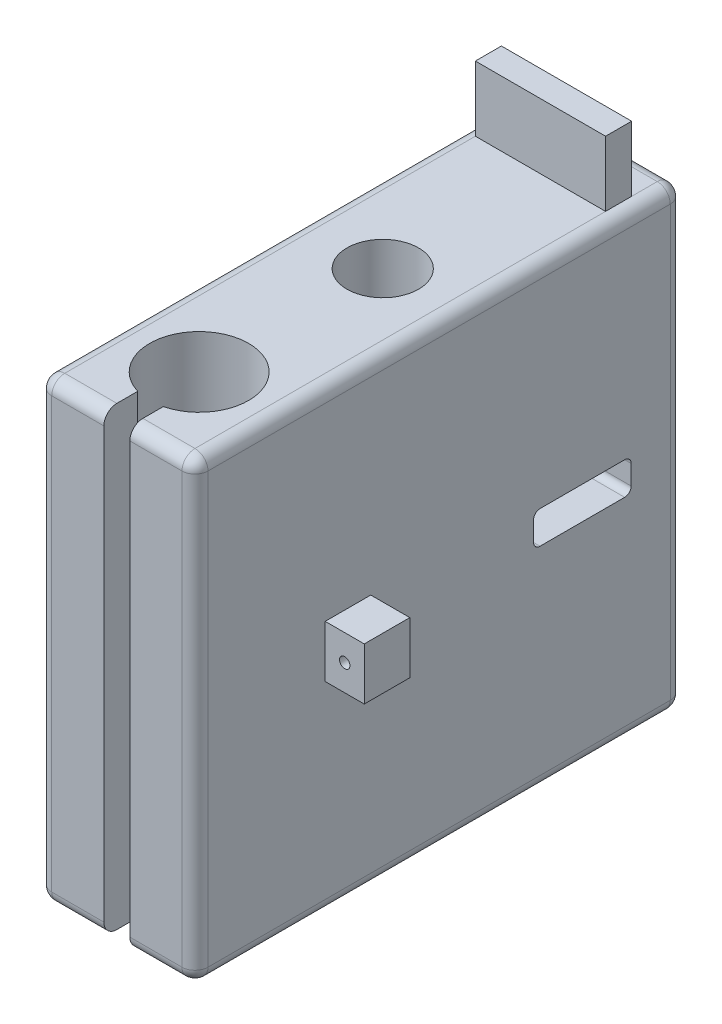
SolidWorks part; units mm, degrees
ref_plane "Front Plane" through (0, 0, 0) normal (0, 0, 1) x (1, 0, 0)
ref_plane "Top Plane" through (0, 0, 0) normal (0, 1, 0) x (1, 0, 0)
ref_plane "Right Plane" through (0, 0, 0) normal (1, 0, 0) x (0, 0, -1)
ref_plane "Plano1" through (-220, 0, 0) normal (1, 0, 0) x (0, 0, -1)
sketch "Esboço1" plane through (-220, 0, 0) normal (1, 0, 0) x (0, 0, -1)
  line L0 (-460.4999, 246.154) -> (-460.4999, 230.354) construction
  line L1 (-465.4999, 248.254) -> (-390.4999, 248.254)
  line L2 (-465.4999, 248.254) -> (-465.4999, 178.254)
  line L3 (-465.4999, 178.254) -> (-390.4999, 178.254)
  line L4 (-390.4999, 248.254) -> (-390.4999, 178.254)
  dimension "D1" = 75
  dimension "D2" = 70
  dimension "D3" = 5
extrude "Ressalto-extrusão1" add sketch "Esboço1" along normal blind 12 and the other way blind 12
sketch "Esboço3" plane through (0, 248.254, 0) normal (0, 1, 0) x (1, 0, 0)
  line L5 (-232, -465.4999) -> (-208, -465.4999) construction
  line L7 (-220, -465.4999) -> (-218, -465.4999)
  line L10 (-218, -465.4999) -> (-218, -460.3692)
  line L11 (-220, -465.4999) -> (-222, -465.4999)
  line L14 (-222, -465.4999) -> (-222, -460.292)
  arc A3 (-218, -460.3692) -> (-222, -460.292) centre (-219.8586, -452.9999) ccw
  circle A8 centre (-219.5085, -425.1499) radius 5.5
  circle A9 centre (-219.5085, -425.1499) radius 5.5
  dimension "D1" = 15.2
  dimension "D3" = 2
  dimension "D4" = 2
  dimension "D2" = 0.5
extrude "Corte-extrusão1" cut sketch "Esboço3" against normal through all
sketch "Esboço4" plane through (0, 0, 390.4999) normal (0, 0, -1) x (-1, 0, 0)
  line L0 (220, 248.254) -> (220, 178.254) construction
  line L1 (232, 248.254) -> (208, 248.254) construction
  line L2 (232, 178.254) -> (208, 178.254) construction
  circle A0 centre (219.8586, 238.254) radius 4.1
  circle A1 centre (219.8586, 188.254) radius 4.1
  dimension "D1" = 8.2
  dimension "D2" = 8.2
extrude "Corte-extrusão2" cut sketch "Esboço4" against normal blind 20
fillet "Filete1" radius 2 14 edges at (-227, 178.254, 465.4999) (-213, 178.254, 465.4999) (-213, 248.254, 465.4999) (-227, 248.254, 465.4999) (-208, 178.254, 427.9999) (-208, 248.254, 427.9999) (-208, 213.254, 465.4999) (-232, 178.254, 427.9999) (-232, 213.254, 465.4999) (-232, 248.254, 427.9999) (-220, 248.254, 390.4999) (-220, 178.254, 390.4999) (-208, 213.254, 390.4999) (-232, 213.254, 390.4999)
sketch "Esboço5" plane through (0, 0, 390.4999) normal (0, 0, -1) x (-1, 0, 0)
  line L8 (214.0164, 195.2585) -> (226.0163, 195.2487)
  line L9 (226.0163, 195.2487) -> (226.0459, 231.2487)
  line L10 (226.0459, 231.2487) -> (214.0459, 231.2585)
  line L11 (214.0459, 231.2585) -> (214.0164, 195.2585)
  line L12 (214.0164, 195.2585) -> (226.0163, 195.2487)
  line L13 (226.0163, 195.2487) -> (226.0459, 231.2487)
  line L14 (226.0459, 231.2487) -> (214.0459, 231.2585)
  line L15 (214.0459, 231.2585) -> (214.0164, 195.2585)
  dimension "D1" = 0
extrude "Corte-extrusão3" cut sketch "Esboço5" against normal blind 29
sketch "Esboço6" plane through (-232, 0, 0) normal (-1, 0, 0) x (0, 0, 1)
  line L0 (392.4999, 213.254) -> (463.4999, 213.254) construction
  line L1 (392.4999, 246.254) -> (392.4999, 180.254) construction
  line L2 (463.4999, 180.254) -> (463.4999, 246.254) construction
  line L3 (398.4999, 213.254) -> (413.4999, 213.254) construction
  line L4 (399.4999, 215.754) -> (412.4999, 215.754)
  line L5 (398.4999, 214.754) -> (398.4999, 211.754)
  line L6 (399.4999, 210.754) -> (412.4999, 210.754)
  line L7 (413.4999, 214.754) -> (413.4999, 211.754)
  arc A0 (412.4999, 215.754) -> (413.4999, 214.754) centre (412.4999, 214.754) cw
  arc A1 (412.4999, 210.754) -> (413.4999, 211.754) centre (412.4999, 211.754) ccw
  arc A2 (398.4999, 211.754) -> (399.4999, 210.754) centre (399.4999, 211.754) ccw
  arc A3 (399.4999, 215.754) -> (398.4999, 214.754) centre (399.4999, 214.754) ccw
  point P14 (413.4999, 215.754)
  point P17 (413.4999, 210.754)
  point P22 (398.4999, 215.754)
  dimension "D4" = 1
  dimension "D1" = 5
  dimension "D2" = 15
  dimension "D3" = 6
extrude "Corte-extrusão4" cut sketch "Esboço6" against normal blind 28
sketch "Esboço7" plane through (-208, 0, 0) normal (1, 0, 0) x (0, 0, -1)
  line L0 (-463.4999, 246.254) -> (-463.4999, 180.254) construction
  line L1 (-445.4999, 217.254) -> (-438.4999, 217.254)
  line L2 (-445.4999, 217.254) -> (-445.4999, 209.254)
  line L3 (-445.4999, 209.254) -> (-438.4999, 209.254)
  line L4 (-438.4999, 217.254) -> (-438.4999, 209.254)
  line L5 (-465.4999, 180.254) -> (-465.4999, 246.254) construction
  point P6 (-463.4999, 213.254)
  point P7 (-445.4999, 213.254)
  dimension "D1" = 7
  dimension "D2" = 8
  dimension "D3" = 20
extrude "Ressalto-extrusão2" add sketch "Esboço7" along normal blind 6 and the other way blind 30
ref_point "Ponto1"
sketch "Esboço9" plane through (0, 0, 445.4999) normal (0, 0, 1) x (1, 0, 0)
  line L0 (-205, 217.254) -> (-205, 209.254) construction
  line L3 (-208, 217.254) -> (-202, 217.254) construction
  line L6 (-208, 209.254) -> (-202, 209.254) construction
  line L7 (-208, 213.254) -> (-202, 213.254) construction
  line L8 (-208, 246.254) -> (-208, 180.254) construction
  line L9 (-202, 217.254) -> (-202, 209.254) construction
hole_wizard "Broca de rosquear para tarraxa de M2x0.41" positions "Esboço13" profile "Esboço14" hole size "M2x0.4" standard "Ansi Metric" end condition through all
sketch "Esboço13" plane through (0, 0, 445.4999) normal (0, 0, 1) x (1, 0, 0)
  line L0 (-205, 217.254) -> (-205, 209.254) construction
  point P0 (-205, 213.254)
sketch "Esboço14" plane through (-205, 213.254, 445.4999) normal (1, 0, 0) x (0, -1, 0)
  line L0 (0, 0) -> (0, 55)
  line L1 (0, 55) -> (0.8, 55)
  line L2 (0.8, 55) -> (0.8, 0)
  line L5 (0.8, 0) -> (0, 0)
  line L11 (0, -6.35) -> (0, 107.95) construction
  dimension "Thru Hole Dia." = 1.6
  dimension "Thru Hole Depth" = 55
sketch "Esboço15" plane through (0, 0, 445.4999) normal (0, 0, 1) x (1, 0, 0)
  line L0 (-235, 217.254) -> (-235, 209.254) construction
  line L1 (-238, 217.254) -> (-232, 217.254) construction
  line L2 (-238, 209.254) -> (-232, 209.254) construction
  line L3 (-238, 213.254) -> (-232, 213.254) construction
  line L4 (-238, 217.254) -> (-238, 209.254) construction
  line L5 (-232, 180.254) -> (-232, 246.254) construction
hole_wizard "Broca de rosquear para tarraxa de M2x0.42" positions "Esboço16" profile "Esboço17" hole size "M2x0.4" standard "Ansi Metric" end condition through all
sketch "Esboço16" plane through (0, 0, 445.4999) normal (0, 0, 1) x (1, 0, 0)
  line L0 (-235, 217.254) -> (-235, 209.254) construction
  point P0 (-235, 213.254)
sketch "Esboço17" plane through (-235, 213.254, 445.4999) normal (1, 0, 0) x (0, -1, 0)
  line L0 (0, 0) -> (0, 55)
  line L1 (0, 55) -> (0.8, 55)
  line L2 (0.8, 55) -> (0.8, 0)
  line L5 (0.8, 0) -> (0, 0)
  line L11 (0, -6.35) -> (0, 107.95) construction
  dimension "Thru Hole Dia." = 1.6
  dimension "Thru Hole Depth" = 55
sketch "Esboço18" plane through (0, 248.254, 0) normal (0, 1, 0) x (1, 0, 0)
  line L0 (-230, -392.4999) -> (-230, -463.4999) construction
  line L1 (-230, -396.4346) -> (-210, -396.4346)
  line L2 (-230, -396.4346) -> (-230, -400.4346)
  line L3 (-230, -400.4346) -> (-210, -400.4346)
  line L4 (-210, -396.4346) -> (-210, -400.4346)
  line L5 (-210, -463.4999) -> (-210, -392.4999) construction
  dimension "D1" = 4
extrude "Ressalto-extrusão3" add sketch "Esboço18" along normal blind 10
